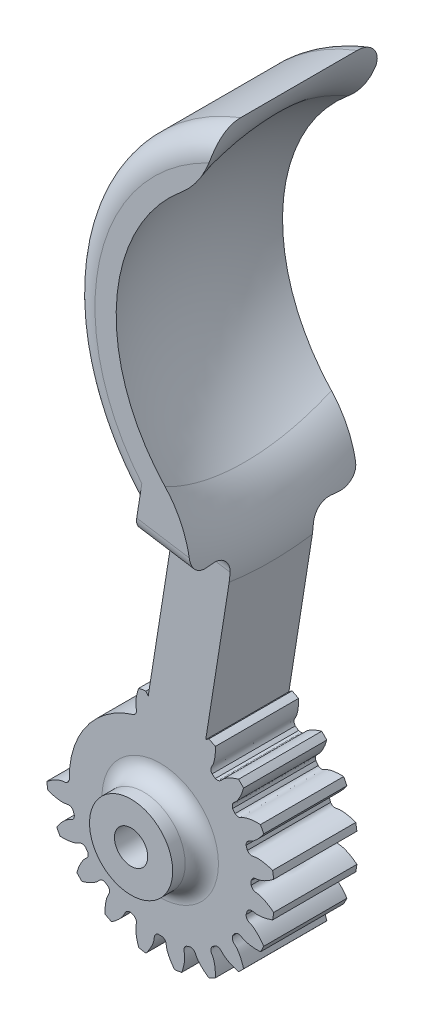
SolidWorks part; units mm, degrees
material "聚脂树脂"
ref_plane "前视基准面" through (0, 0, 0) normal (0, 0, 1) x (1, 0, 0)
ref_plane "上视基准面" through (0, 0, 0) normal (0, 1, 0) x (1, 0, 0)
ref_plane "右视基准面" through (0, 0, 0) normal (1, 0, 0) x (0, 0, -1)
other "Configuration Table"
sketch "草图1" plane through (0, 0, 0) normal (0, 0, 1) x (1, 0, 0)
  circle A0 centre (0, 0) radius 13.75
extrude "凸台-拉伸1" add sketch "草图1" along normal blind 10
ref_axis "基准轴1" through (0, 0, -1.5) along (0, 0, 1)
sketch "草图2" plane through (0, 0, 0) normal (0, 0, 1) x (1, 0, 0)
  line L0 (0, 0) -> (0, 13.75) construction
  circle A0 centre (0, 0) radius 13.75 construction
  arc A1 (0.2416, 10.9348) -> (-0.2416, 10.9348) centre (0, 0) ccw
  arc A2 (3.9764, 15.6228) -> (-3.9764, 15.6228) centre (0, 0) ccw
  spline S0 degree 3 poles (0.2416, 10.9348) (0.764, 11.1168) (0.6964, 11.4839) (0.7661, 11.8375) (0.7736, 11.8719) (0.7829, 11.9108) (0.7941, 11.954) (0.8075, 12.0015) (0.8231, 12.0532) (0.8413, 12.1091) (0.8621, 12.169) (0.8857, 12.2329) (0.9123, 12.3007) (0.9421, 12.3723) (0.9752, 12.4476) (1.0117, 12.5264) (1.0519, 12.6088) (1.0959, 12.6945) (1.1438, 12.7834) (1.1957, 12.8755) (1.2519, 12.9705) (1.3125, 13.0684) (1.3775, 13.1691) (1.4472, 13.2723) (1.5216, 13.3779) (1.601, 13.4858) (1.6853, 13.5958) (1.7747, 13.7078) (1.8694, 13.8216) (1.9693, 13.937) (2.0748, 14.0539) (2.1857, 14.1721) (2.3023, 14.2914) (2.4246, 14.4116) (2.5527, 14.5326) (2.6866, 14.6542) (2.8265, 14.7761) (2.9725, 14.8983) (3.1245, 15.0204) (3.2826, 15.1424) (3.4469, 15.2639) (3.6768, 15.427) (3.8549, 15.5454) (3.9764, 15.6228) knots 0 0 0 0 0.165916 0.170906 0.176664 0.183189 0.190482 0.198542 0.207371 0.216967 0.22733 0.238462 0.250361 0.263027 0.276462 0.290664 0.305634 0.321371 0.337876 0.355149 0.37319 0.391998 0.411574 0.431917 0.453028 0.474907 0.497554 0.520968 0.54515 0.570099 0.595817 0.622302 0.649554 0.677575 0.706363 0.735918 0.766242 0.797333 0.829191 0.861818 0.895212 0.929373 1 1 1 1
  spline S1 degree 3 poles (-0.2416, 10.9348) (-0.764, 11.1168) (-0.6964, 11.4839) (-0.7661, 11.8375) (-0.7736, 11.8719) (-0.7829, 11.9108) (-0.7941, 11.954) (-0.8075, 12.0015) (-0.8231, 12.0532) (-0.8413, 12.1091) (-0.8621, 12.169) (-0.8857, 12.2329) (-0.9123, 12.3007) (-0.9421, 12.3723) (-0.9752, 12.4476) (-1.0117, 12.5264) (-1.0519, 12.6088) (-1.0959, 12.6945) (-1.1438, 12.7834) (-1.1957, 12.8755) (-1.2519, 12.9705) (-1.3125, 13.0684) (-1.3775, 13.1691) (-1.4472, 13.2723) (-1.5216, 13.3779) (-1.601, 13.4858) (-1.6853, 13.5958) (-1.7747, 13.7078) (-1.8694, 13.8216) (-1.9693, 13.937) (-2.0748, 14.0539) (-2.1857, 14.1721) (-2.3023, 14.2914) (-2.4246, 14.4116) (-2.5527, 14.5326) (-2.6866, 14.6542) (-2.8265, 14.7761) (-2.9725, 14.8983) (-3.1245, 15.0204) (-3.2826, 15.1424) (-3.4469, 15.2639) (-3.6768, 15.427) (-3.8549, 15.5454) (-3.9764, 15.6228) knots 0 0 0 0 0.165916 0.170906 0.176664 0.183189 0.190482 0.198542 0.207371 0.216967 0.22733 0.238462 0.250361 0.263027 0.276462 0.290664 0.305634 0.321371 0.337876 0.355149 0.37319 0.391998 0.411574 0.431917 0.453028 0.474907 0.497554 0.520968 0.54515 0.570099 0.595817 0.622302 0.649554 0.677575 0.706363 0.735918 0.766242 0.797333 0.829191 0.861818 0.895212 0.929373 1 1 1 1
extrude "切除-拉伸1" cut sketch "草图2" along normal through all
pattern_circular "阵列(圆周)1" count 20 every 18 about axis through (0, 0, -1.5) along (0, 0, 1) of "切除-拉伸1"
sketch "草图3" plane through (0, 0, 0) normal (0, 0, 1) x (1, 0, 0)
  circle A0 centre (0, 0) radius 12.5 construction
  dimension "Dn" = 25
sketch "草图6" plane through (0, 0, 0) normal (0, 0, -1) x (-1, 0, 0)
  line L0 (0, 0) -> (-10.311, 65.1009) construction
  line L1 (0, 0) -> (38.9643, 6.1713) construction
  line L2 (0, 0) -> (-30.4582, -4.8241) construction
  line L3 (-12.3461, -1.9554) -> (-21.1812, 53.827) construction
  line L4 (3.4569, 0.5475) -> (-2.1703, 36.0761)
  line L5 (-3.4569, -0.5475) -> (-9.0841, 34.981)
  line L6 (-9.0841, 34.981) -> (-15.0031, 72.3522)
  line L7 (-15.0031, 72.3522) -> (-21.4537, 55.5478) construction
  line L8 (-15.0031, 72.3522) -> (-7.9754, 90.6601) construction
  line L9 (-15.0031, 72.3522) -> (-11.6329, 81.132)
  line L10 (-3.4569, -0.5475) -> (3.4569, 0.5475)
  circle A0 centre (0, 0) radius 12.5 construction
  circle A1 centre (-21.4537, 55.5478) radius 24 construction
  circle A2 centre (-21.4537, 55.5478) radius 27.4044 construction
  arc A3 (-11.6329, 81.132) -> (-2.1703, 36.0761) centre (-21.4537, 55.5478) cw
  dimension "D1" = 25
  dimension "D4" = 48
  dimension "D5" = 30
  dimension "D2" = 7
  dimension "D3" = 58.22
extrude "凸台-拉伸2" add sketch "草图6" against normal blind 15 and the other way blind 5 contours A3 L9 L6 L5 L10 L4 | L5 | L4 region at (4.141, 46.7727, 0)
sketch "草图7" plane through (3.4569, -0.5475, 0) normal (0.9877, -0.1564, 0) x (0, 0, -1)
  line L0 (0, 0) -> (0, 34)
  line L1 (0, 34) -> (5, 34)
  line L2 (5, 0) -> (5, 73.8085) construction
  line L3 (5, 34) -> (5, 0)
  line L4 (5, 0) -> (0, 0) construction
  line L5 (5, 0) -> (5, 73.8085) construction
  line L6 (5, 0) -> (0, 0)
  line L7 (-5, 4.6588) -> (-5, 27.3083) construction
  line L8 (-10, 4.6588) -> (0, 4.6588) construction
  line L9 (-15, 34) -> (-15, 0)
  line L10 (-10, 34) -> (-15, 34)
  line L11 (-10, 0) -> (-10, 34)
  line L12 (-15, 0) -> (-10, 0)
  dimension "D1" = 34
extrude "切除-拉伸3" cut sketch "草图7" against normal blind 32 and the other way blind 10
ref_plane "基准面1" through (12.5, 0, 0) normal (1, 0, 0) x (0, 0, -1)
ref_axis "基准轴2" through (0, 0, -6) along (0, 0, 1)
ref_plane "基准面2" through (0, 0, 0) normal (-0.9877, 0.1564, 0) x (0, 0, 1)
ref_plane "基准面3" through (12.3461, -1.9554, 0) normal (-0.9877, 0.1564, 0) x (0, 0, 1)
sketch "草图13" plane through (12.3461, -1.9554, 0) normal (-0.9877, 0.1564, 0) x (0, 0, 1)
  line L0 (5, 0.4331) -> (5, 90.5431) construction
  line L1 (0, 0.4331) -> (10, 0.4331) construction
  line L2 (5, 82.6531) -> (5, 34.6531)
  arc A0 (5, 82.6531) -> (5, 34.6531) centre (5, 58.6531) cw
  dimension "D1" = 24
  dimension "D2" = 58.22
revolve "切除-旋转2" cut sketch "草图13" angle 360 about L0
sketch "草图12" plane through (0, 0, -5) normal (0, 0, -1) x (-1, 0, 0)
  line L0 (0, 0) -> (-14.3434, 90.5607) construction
  line L1 (-12.3461, -1.9554) -> (-26.4984, 87.3984) construction
  line L2 (-11.6703, 81.0345) -> (-11.6329, 81.132)
  line L3 (0, 0) -> (-28.4747, -4.5099) construction
  line L4 (-2.1703, 36.0761) -> (-2.1904, 36.2032)
  line L5 (-1.8619, 34.1289) -> (-2.1703, 36.0761) construction
  line L6 (-13.501, 76.2653) -> (-11.6329, 81.132) construction
  circle A0 centre (-21.4537, 55.5478) radius 28.3019
  circle A1 centre (-21.4537, 55.5478) radius 27.3
  line M6 (-11.6329, 81.132) -> (-13.501, 76.2653)
  arc M11 (-2.1703, 36.0761) -> (-11.6329, 81.132) centre (-21.4537, 55.5478) ccw
  dimension "D3" = 54.6
  dimension "D4" = 56.6039
  dimension "D1" = 12.5
  dimension "D2" = 58.22
extrude "切除-拉伸4" cut sketch "草图12" against normal blind 22 contours A1 M11 M6 region at (11.1999, 80.9099, -5)
fillet "圆角2" radius 2 4 edges at (5.3188, 33.5814, 10) (5.3188, 33.5814, 15) (5.3188, 33.5814, 0) (5.3188, 33.5814, -5)
fillet "圆角3" radius 3 2 edges at (-5.2557, 61.1957, 15) (-5.2557, 61.1957, -5)
sketch "草图16" plane through (0, 0, 10) normal (0, 0, 1) x (1, 0, 0)
  circle A0 centre (0, 0) radius 2
  dimension "D1" = 4
extrude "切除-拉伸5" cut sketch "草图16" against normal blind 16.5
sketch "草图18" plane through (0, 0, 10) normal (0, 0, 1) x (1, 0, 0)
  circle A0 centre (0, 0) radius 5
  circle A1 centre (0, 0) radius 2
  dimension "D1" = 10
  dimension "D2" = 4
extrude "凸台-拉伸4" add sketch "草图18" along normal blind 3.5
sketch "草图19" plane through (0, 0, 0) normal (0, 0, -1) x (-1, 0, 0)
  circle A0 centre (0, 0) radius 8
  dimension "D1" = 16
extrude "切除-拉伸7" cut sketch "草图19" against normal blind 3
fillet "圆角4" radius 2 1 edges at (5, 0, 10)
sketch "草图20" plane through (0, 0, 0) normal (0, 0, -1) x (-1, 0, 0)
  line L0 (0, 0) -> (3.6089, 10.325)
  line L1 (3.6089, 10.325) -> (7.1451, 20.4421)
  line L2 (0, 0) -> (10.9348, -0.2416)
  line L3 (10.9348, -0.2416) -> (20.7519, -0.2416)
  circle A0 centre (0, 0) radius 17.5
  circle A1 centre (0, 0) radius 10.9375
  arc A2 (-8.7044, 6.6228) -> (-8.9885, 6.2318) centre (0, 0) ccw construction
  dimension "D1" = 35
extrude "切除-拉伸8" cut sketch "草图20" against normal blind 10 contours A1 L3 A0 L1 region at (-11.1082, 7.7459, 0)
fillet "圆角5" radius 10 2 edges at (9.1518, 35.4088, 5) (12.7188, 78.303, 5)
